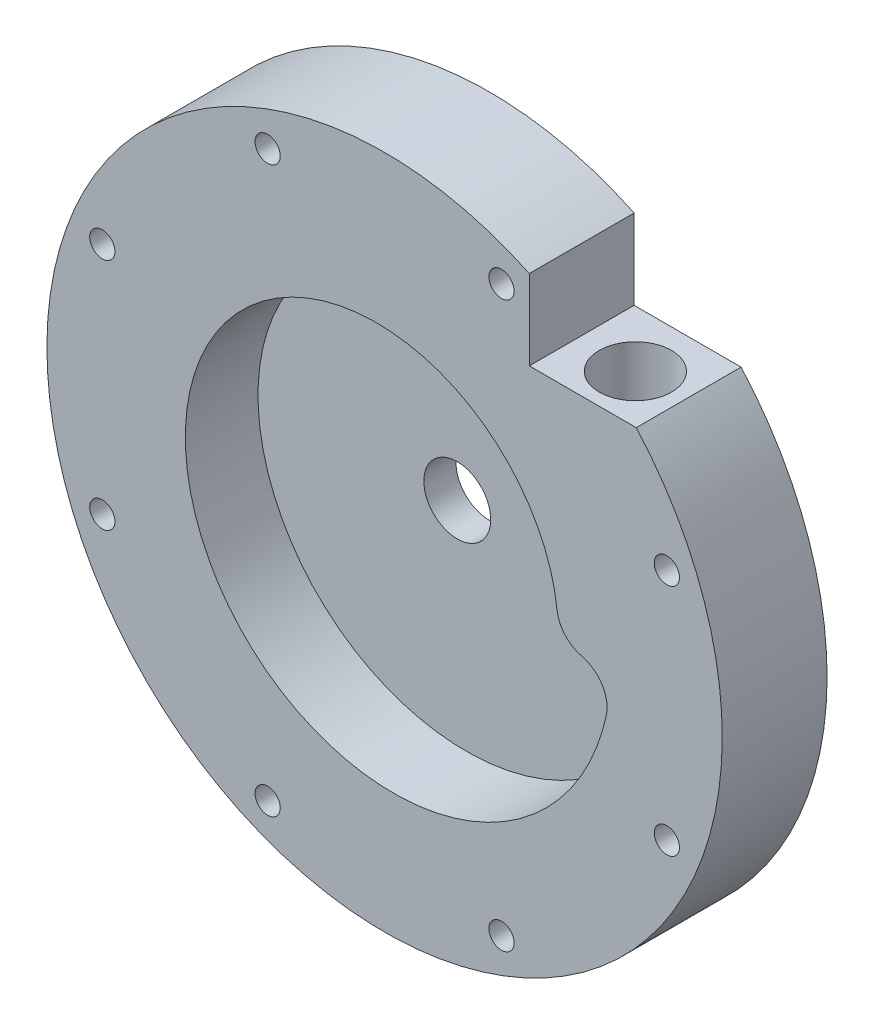
SolidWorks part; units mm, degrees
material "6061-T6 (SS)"
ref_plane "Front Plane" through (0, 0, 0) normal (0, 0, 1) x (1, 0, 0)
ref_plane "Top Plane" through (0, 0, 0) normal (0, 1, 0) x (1, 0, 0)
ref_plane "Right Plane" through (0, 0, 0) normal (1, 0, 0) x (0, 0, -1)
sketch "Sketch22" plane through (0, 0, 0) normal (0, 1, 0) x (1, 0, 0)
  line L0 (-25.4, 0) -> (-6.604, 0)
  line L1 (-25.4, 0) -> (-25.4, -14.351)
  line L2 (-17.4625, 6.35) -> (-17.4625, 4.7625)
  line L3 (-25.4, -14.351) -> (-66.675, -14.351)
  line L4 (-66.675, -14.351) -> (-66.675, 6.35)
  line L9 (-17.4625, 6.35) -> (-66.675, 6.35)
  line L10 (0, 0) -> (0, 9.525) construction
  line L11 (-6.604, 6.35) -> (-6.604, 0)
  line L12 (-17.4625, 4.7625) -> (-11.1125, 4.7625)
  line L15 (-11.1125, 4.7625) -> (-11.1125, 6.35)
  line L16 (-11.1125, 6.35) -> (-6.604, 6.35)
  dimension "D1" = 6.35
  dimension "D2" = 6.35
  dimension "D3" = 20.701
  dimension "D4" = 22.225
  dimension "D5" = 50.8
  dimension "D6" = 133.35
  dimension "D7" = 13.208
  dimension "D8" = 1.5875
revolve "Main Body" add sketch "Sketch22" angle 360 about L10
curve "Volute Spiral"
  spline degree 3 poles (34.2618, 0, 0) (34.2648, 0.0718, 0) (34.2707, 0.2156, 0) (34.2778, 0.4312, 0) (34.2837, 0.647, 0) (34.2882, 0.8628, 0) (34.2914, 1.0787, 0) (34.2932, 1.2947, 0) (34.2937, 1.5108, 0) (34.2929, 1.7269, 0) (34.2907, 1.9431, 0) (34.2871, 2.1593, 0) (34.2822, 2.3756, 0) (34.2759, 2.5919, 0) (34.2683, 2.8082, 0) (34.2593, 3.0245, 0) (34.2489, 3.2407, 0) (34.2372, 3.457, 0) (34.2242, 3.6733, 0) (34.2098, 3.8895, 0) (34.194, 4.1058, 0) (34.1768, 4.3219, 0) (34.1583, 4.538, 0) (34.1385, 4.7541, 0) (34.1173, 4.9701, 0) (34.0947, 5.186, 0) (34.0708, 5.4018, 0) (34.0454, 5.6175, 0) (34.0188, 5.8331, 0) (33.9908, 6.0486, 0) (33.9614, 6.264, 0) (33.9306, 6.4793, 0) (33.8985, 6.6944, 0) (33.8651, 6.9094, 0) (33.8303, 7.1242, 0) (33.7941, 7.3388, 0) (33.7566, 7.5533, 0) (33.7177, 7.7676, 0) (33.6774, 7.9817, 0) (33.6358, 8.1956, 0) (33.5929, 8.4093, 0) (33.5486, 8.6228, 0) (33.5029, 8.8361, 0) (33.4559, 9.0491, 0) (33.4076, 9.2619, 0) (33.3579, 9.4745, 0) (33.3068, 9.6868, 0) (33.2544, 9.8988, 0) (33.2006, 10.1105, 0) (33.1456, 10.322, 0) (33.0891, 10.5332, 0) (33.0313, 10.744, 0) (32.9722, 10.9546, 0) (32.9118, 11.1648, 0) (32.85, 11.3748, 0) (32.7869, 11.5843, 0) (32.7224, 11.7936, 0) (32.6566, 12.0025, 0) (32.5895, 12.211, 0) (32.521, 12.4192, 0) (32.4513, 12.627, 0) (32.3802, 12.8344, 0) (32.3077, 13.0414, 0) (32.234, 13.248, 0) (32.1589, 13.4542, 0) (32.0826, 13.6599, 0) (32.0049, 13.8653, 0) (31.9259, 14.0702, 0) (31.8456, 14.2747, 0) (31.764, 14.4787, 0) (31.6811, 14.6823, 0) (31.5968, 14.8854, 0) (31.5113, 15.088, 0) (31.4245, 15.2901, 0) (31.3364, 15.4917, 0) (31.247, 15.6929, 0) (31.1563, 15.8935, 0) (31.0644, 16.0936, 0) (30.9711, 16.2932, 0) (30.8766, 16.4922, 0) (30.7808, 16.6907, 0) (30.6837, 16.8886, 0) (30.5854, 17.086, 0) (30.4858, 17.2829, 0) (30.3849, 17.4791, 0) (30.2828, 17.6748, 0) (30.1794, 17.8698, 0) (30.0747, 18.0643, 0) (29.9688, 18.2582, 0) (29.8617, 18.4514, 0) (29.7533, 18.644, 0) (29.6437, 18.836, 0) (29.5328, 19.0274, 0) (29.4208, 19.2181, 0) (29.3074, 19.4081, 0) (29.1929, 19.5975, 0) (29.0771, 19.7862, 0) (28.9601, 19.9742, 0) (28.842, 20.1616, 0) (28.7226, 20.3482, 0) (28.602, 20.5342, 0) (28.4801, 20.7194, 0) (28.3571, 20.904, 0) (28.233, 21.0877, 0) (28.1076, 21.2708, 0) (27.981, 21.4531, 0) (27.8533, 21.6347, 0) (27.7243, 21.8155, 0) (27.5942, 21.9956, 0) (27.463, 22.1748, 0) (27.3306, 22.3533, 0) (27.197, 22.531, 0) (27.0623, 22.708, 0) (26.9264, 22.8841, 0) (26.7894, 23.0594, 0) (26.6512, 23.2339, 0) (26.5119, 23.4075, 0) (26.3715, 23.5804, 0) (26.23, 23.7524, 0) (26.0873, 23.9235, 0) (25.9435, 24.0938, 0) (25.7987, 24.2632, 0) (25.6527, 24.4318, 0) (25.5056, 24.5995, 0) (25.3574, 24.7663, 0) (25.2082, 24.9322, 0) (25.0578, 25.0973, 0) (24.9064, 25.2614, 0) (24.7539, 25.4246, 0) (24.6003, 25.5869, 0) (24.4457, 25.7483, 0) (24.29, 25.9087, 0) (24.1333, 26.0682, 0) (23.9755, 26.2268, 0) (23.8167, 26.3844, 0) (23.6569, 26.541, 0) (23.496, 26.6967, 0) (23.3341, 26.8514, 0) (23.1712, 27.0051, 0) (23.0073, 27.1579, 0) (22.8424, 27.3096, 0) (22.6765, 27.4604, 0) (22.5096, 27.6101, 0) (22.3417, 27.7589, 0) (22.1728, 27.9066, 0) (22.003, 28.0533, 0) (21.8322, 28.199, 0) (21.6604, 28.3436, 0) (21.4877, 28.4872, 0) (21.314, 28.6297, 0) (21.1394, 28.7712, 0) (20.9639, 28.9116, 0) (20.7874, 29.051, 0) (20.61, 29.1892, 0) (20.4317, 29.3264, 0) (20.2524, 29.4626, 0) (20.0723, 29.5976, 0) (19.8913, 29.7315, 0) (19.7094, 29.8643, 0) (19.5266, 29.996, 0) (19.3429, 30.1266, 0) (19.1584, 30.2561, 0) (18.973, 30.3844, 0) (18.7867, 30.5116, 0) (18.5996, 30.6377, 0) (18.4117, 30.7626, 0) (18.2229, 30.8864, 0) (18.0333, 31.009, 0) (17.8429, 31.1304, 0) (17.6516, 31.2507, 0) (17.4596, 31.3698, 0) (17.2667, 31.4878, 0) (17.0731, 31.6045, 0) (16.8786, 31.7201, 0) (16.6834, 31.8344, 0) (16.4875, 31.9476, 0) (16.2907, 32.0596, 0) (16.0932, 32.1703, 0) (15.895, 32.2799, 0) (15.696, 32.3882, 0) (15.4963, 32.4953, 0) (15.2959, 32.6012, 0) (15.0947, 32.7058, 0) (14.8929, 32.8092, 0) (14.6903, 32.9114, 0) (14.487, 33.0123, 0) (14.2831, 33.1119, 0) (14.0784, 33.2103, 0) (13.8731, 33.3075, 0) (13.6672, 33.4033, 0) (13.4606, 33.4979, 0) (13.2533, 33.5912, 0) (13.0454, 33.6833, 0) (12.8368, 33.774, 0) (12.6277, 33.8635, 0) (12.4179, 33.9517, 0) (12.2075, 34.0385, 0) (11.9965, 34.1241, 0) (11.7849, 34.2084, 0) (11.5727, 34.2913, 0) (11.36, 34.373, 0) (11.1467, 34.4533, 0) (10.9328, 34.5323, 0) (10.7183, 34.61, 0) (10.5034, 34.6863, 0) (10.2879, 34.7613, 0) (10.0718, 34.835, 0) (9.8553, 34.9074, 0) (9.6382, 34.9783, 0) (9.4206, 35.048, 0) (9.2025, 35.1163, 0) (8.984, 35.1832, 0) (8.765, 35.2488, 0) (8.5455, 35.313, 0) (8.3255, 35.3759, 0) (8.1051, 35.4374, 0) (7.8842, 35.4975, 0) (7.6629, 35.5562, 0) (7.4412, 35.6136, 0) (7.2191, 35.6696, 0) (6.9965, 35.7242, 0) (6.7736, 35.7774, 0) (6.5503, 35.8292, 0) (6.3265, 35.8796, 0) (6.1024, 35.9287, 0) (5.878, 35.9763, 0) (5.6532, 36.0225, 0) (5.428, 36.0674, 0) (5.2025, 36.1108, 0) (4.9766, 36.1528, 0) (4.7505, 36.1934, 0) (4.524, 36.2326, 0) (4.2972, 36.2704, 0) (4.0701, 36.3067, 0) (3.8428, 36.3417, 0) (3.6151, 36.3752, 0) (3.3872, 36.4073, 0) (3.159, 36.438, 0) (2.9306, 36.4672, 0) (2.7019, 36.495, 0) (2.473, 36.5214, 0) (2.2439, 36.5463, 0) (2.0146, 36.5699, 0) (1.785, 36.5919, 0) (1.5553, 36.6126, 0) (1.3253, 36.6318, 0) (1.0952, 36.6495, 0) (0.8649, 36.6658, 0) (0.6345, 36.6807, 0) (0.4039, 36.6941, 0) (0.1731, 36.706, 0) (-0.0577, 36.7166, 0) (-0.2887, 36.7256, 0) (-0.5199, 36.7332, 0) (-0.7511, 36.7394, 0) (-0.9824, 36.7441, 0) (-1.2138, 36.7474, 0) (-1.4453, 36.7492, 0) (-1.6769, 36.7495, 0) (-1.9085, 36.7484, 0) (-2.1402, 36.7458, 0) (-2.3719, 36.7418, 0) (-2.6037, 36.7363, 0) (-2.8355, 36.7293, 0) (-3.0673, 36.7209, 0) (-3.2991, 36.711, 0) (-3.5309, 36.6997, 0) (-3.7627, 36.6869, 0) (-3.9944, 36.6726, 0) (-4.2262, 36.6569, 0) (-4.4579, 36.6397, 0) (-4.6895, 36.6211, 0) (-4.9211, 36.6009, 0) (-5.1526, 36.5794, 0) (-5.3841, 36.5563, 0) (-5.6154, 36.5318, 0) (-5.8467, 36.5059, 0) (-6.0779, 36.4784, 0) (-6.3089, 36.4495, 0) (-6.5399, 36.4192, 0) (-6.7706, 36.3874, 0) (-7.0013, 36.3541, 0) (-7.2318, 36.3194, 0) (-7.4621, 36.2832, 0) (-7.6923, 36.2455, 0) (-7.9223, 36.2064, 0) (-8.1521, 36.1658, 0) (-8.3817, 36.1238, 0) (-8.6111, 36.0803, 0) (-8.8403, 36.0354, 0) (-9.0693, 35.989, 0) (-9.298, 35.9411, 0) (-9.5265, 35.8918, 0) (-9.7548, 35.8411, 0) (-9.9827, 35.7889, 0) (-10.2105, 35.7352, 0) (-10.4379, 35.6802, 0) (-10.665, 35.6236, 0) (-10.8919, 35.5656, 0) (-11.1184, 35.5062, 0) (-11.3446, 35.4453, 0) (-11.5705, 35.383, 0) (-11.7961, 35.3193, 0) (-12.0213, 35.2541, 0) (-12.2461, 35.1875, 0) (-12.4706, 35.1194, 0) (-12.6948, 35.0499, 0) (-12.9185, 34.979, 0) (-13.1419, 34.9067, 0) (-13.3648, 34.8329, 0) (-13.5874, 34.7578, 0) (-13.8095, 34.6812, 0) (-14.0312, 34.6031, 0) (-14.2525, 34.5237, 0) (-14.4734, 34.4429, 0) (-14.6937, 34.3606, 0) (-14.9137, 34.2769, 0) (-15.1331, 34.1918, 0) (-15.3521, 34.1054, 0) (-15.5706, 34.0175, 0) (-15.7885, 33.9282, 0) (-16.006, 33.8375, 0) (-16.223, 33.7455, 0) (-16.4394, 33.652, 0) (-16.6553, 33.5572, 0) (-16.8707, 33.461, 0) (-17.0855, 33.3634, 0) (-17.2997, 33.2644, 0) (-17.5134, 33.164, 0) (-17.7265, 33.0623, 0) (-17.939, 32.9592, 0) (-18.151, 32.8548, 0) (-18.3623, 32.7489, 0) (-18.573, 32.6418, 0) (-18.7831, 32.5332, 0) (-18.9925, 32.4234, 0) (-19.2014, 32.3121, 0) (-19.4095, 32.1996, 0) (-19.6171, 32.0857, 0) (-19.8239, 31.9704, 0) (-20.0301, 31.8538, 0) (-20.2356, 31.7359, 0) (-20.4404, 31.6167, 0) (-20.6445, 31.4962, 0) (-20.8479, 31.3743, 0) (-21.0506, 31.2511, 0) (-21.2526, 31.1267, 0) (-21.4538, 31.0009, 0) (-21.6543, 30.8738, 0) (-21.854, 30.7454, 0) (-22.053, 30.6158, 0) (-22.2512, 30.4848, 0) (-22.4487, 30.3526, 0) (-22.6453, 30.2191, 0) (-22.8412, 30.0843, 0) (-23.0363, 29.9482, 0) (-23.2305, 29.8109, 0) (-23.424, 29.6723, 0) (-23.6166, 29.5325, 0) (-23.8084, 29.3915, 0) (-23.9994, 29.2491, 0) (-24.1895, 29.1056, 0) (-24.3787, 28.9608, 0) (-24.5671, 28.8148, 0) (-24.7546, 28.6676, 0) (-24.9413, 28.5191, 0) (-25.127, 28.3694, 0) (-25.3119, 28.2186, 0) (-25.4958, 28.0665, 0) (-25.6789, 27.9132, 0) (-25.861, 27.7587, 0) (-26.0422, 27.6031, 0) (-26.2224, 27.4463, 0) (-26.4018, 27.2882, 0) (-26.5801, 27.1291, 0) (-26.7576, 26.9687, 0) (-26.934, 26.8072, 0) (-27.1095, 26.6446, 0) (-27.284, 26.4808, 0) (-27.4575, 26.3159, 0) (-27.63, 26.1498, 0) (-27.8015, 25.9826, 0) (-27.972, 25.8143, 0) (-28.1415, 25.6448, 0) (-28.31, 25.4743, 0) (-28.4774, 25.3027, 0) (-28.6438, 25.1299, 0) (-28.8092, 24.9561, 0) (-28.9735, 24.7811, 0) (-29.1367, 24.6051, 0) (-29.2989, 24.4281, 0) (-29.46, 24.2499, 0) (-29.62, 24.0707, 0) (-29.7789, 23.8905, 0) (-29.9368, 23.7092, 0) (-30.0935, 23.5268, 0) (-30.2491, 23.3435, 0) (-30.4036, 23.1591, 0) (-30.557, 22.9737, 0) (-30.7093, 22.7872, 0) (-30.8604, 22.5998, 0) (-31.0104, 22.4114, 0) (-31.1592, 22.2219, 0) (-31.3069, 22.0315, 0) (-31.4534, 21.8402, 0) (-31.5988, 21.6478, 0) (-31.7429, 21.4545, 0) (-31.8859, 21.2602, 0) (-32.0277, 21.065, 0) (-32.1684, 20.8688, 0) (-32.3078, 20.6717, 0) (-32.446, 20.4737, 0) (-32.583, 20.2747, 0) (-32.7188, 20.0748, 0) (-32.8533, 19.8741, 0) (-32.9866, 19.6724, 0) (-33.1187, 19.4698, 0) (-33.2496, 19.2664, 0) (-33.3792, 19.0621, 0) (-33.5075, 18.8569, 0) (-33.6346, 18.6509, 0) (-33.7604, 18.444, 0) (-33.885, 18.2362, 0) (-34.0082, 18.0276, 0) (-34.1302, 17.8182, 0) (-34.2509, 17.608, 0) (-34.3703, 17.397, 0) (-34.4884, 17.1851, 0) (-34.6052, 16.9725, 0) (-34.7207, 16.7591, 0) (-34.8349, 16.5449, 0) (-34.9478, 16.3299, 0) (-35.0593, 16.1141, 0) (-35.1695, 15.8976, 0) (-35.2784, 15.6804, 0) (-35.3859, 15.4624, 0) (-35.4921, 15.2436, 0) (-35.597, 15.0242, 0) (-35.7004, 14.804, 0) (-35.8026, 14.5832, 0) (-35.9033, 14.3616, 0) (-36.0027, 14.1393, 0) (-36.1007, 13.9164, 0) (-36.1973, 13.6928, 0) (-36.2926, 13.4685, 0) (-36.3864, 13.2436, 0) (-36.4789, 13.018, 0) (-36.57, 12.7918, 0) (-36.6596, 12.5649, 0) (-36.7479, 12.3374, 0) (-36.8348, 12.1094, 0) (-36.9202, 11.8807, 0) (-37.0042, 11.6514, 0) (-37.0868, 11.4215, 0) (-37.168, 11.1911, 0) (-37.2477, 10.96, 0) (-37.326, 10.7285, 0) (-37.4029, 10.4963, 0) (-37.4783, 10.2637, 0) (-37.5523, 10.0305, 0) (-37.6248, 9.7967, 0) (-37.6959, 9.5625, 0) (-37.7655, 9.3277, 0) (-37.8337, 9.0925, 0) (-37.9004, 8.8568, 0) (-37.9656, 8.6205, 0) (-38.0293, 8.3839, 0) (-38.0916, 8.1467, 0) (-38.1524, 7.9091, 0) (-38.2117, 7.6711, 0) (-38.2696, 7.4326, 0) (-38.3259, 7.1937, 0) (-38.3808, 6.9544, 0) (-38.4342, 6.7147, 0) (-38.486, 6.4746, 0) (-38.5364, 6.2341, 0) (-38.5853, 5.9932, 0) (-38.6326, 5.7519, 0) (-38.6785, 5.5103, 0) (-38.7229, 5.2684, 0) (-38.7657, 5.0261, 0) (-38.807, 4.7835, 0) (-38.8468, 4.5405, 0) (-38.8851, 4.2973, 0) (-38.9219, 4.0537, 0) (-38.9571, 3.8099, 0) (-38.9908, 3.5657, 0) (-39.023, 3.3213, 0) (-39.0537, 3.0767, 0) (-39.0828, 2.8317, 0) (-39.1104, 2.5866, 0) (-39.1364, 2.3412, 0) (-39.1609, 2.0955, 0) (-39.1839, 1.8497, 0) (-39.2053, 1.6037, 0) (-39.2252, 1.3574, 0) (-39.2435, 1.111, 0) (-39.2603, 0.8644, 0) (-39.2756, 0.6176, 0) (-39.2893, 0.3707, 0) (-39.3014, 0.1236, 0) (-39.312, -0.1236, 0) (-39.321, -0.371, 0) (-39.3285, -0.6185, 0) (-39.3344, -0.866, 0) (-39.3388, -1.1137, 0) (-39.3416, -1.3615, 0) (-39.3428, -1.6093, 0) (-39.3425, -1.8572, 0) (-39.3406, -2.1052, 0) (-39.3372, -2.3532, 0) (-39.3322, -2.6013, 0) (-39.3257, -2.8494, 0) (-39.3175, -3.0975, 0) (-39.3078, -3.3456, 0) (-39.2966, -3.5937, 0) (-39.2838, -3.8418, 0) (-39.2694, -4.0899, 0) (-39.2534, -4.338, 0) (-39.2359, -4.586, 0) (-39.2168, -4.834, 0) (-39.1962, -5.0819, 0) (-39.174, -5.3298, 0) (-39.1502, -5.5776, 0) (-39.1248, -5.8252, 0) (-39.0979, -6.0728, 0) (-39.0694, -6.3203, 0) (-39.0394, -6.5677, 0) (-39.0078, -6.8149, 0) (-38.9746, -7.062, 0) (-38.9399, -7.309, 0) (-38.9036, -7.5558, 0) (-38.8657, -7.8024, 0) (-38.8263, -8.0488, 0) (-38.7853, -8.2951, 0) (-38.7427, -8.5411, 0) (-38.6986, -8.787, 0) (-38.653, -9.0326, 0) (-38.6057, -9.2781, 0) (-38.557, -9.5232, 0) (-38.5066, -9.7682, 0) (-38.4547, -10.0128, 0) (-38.4013, -10.2572, 0) (-38.3463, -10.5014, 0) (-38.2897, -10.7452, 0) (-38.2316, -10.9888, 0) (-38.172, -11.232, 0) (-38.1108, -11.475, 0) (-38.048, -11.7176, 0) (-37.9838, -11.9598, 0) (-37.9179, -12.2018, 0) (-37.8506, -12.4433, 0) (-37.7817, -12.6845, 0) (-37.7112, -12.9254, 0) (-37.6393, -13.1658, 0) (-37.5658, -13.4059, 0) (-37.4907, -13.6455, 0) (-37.4142, -13.8848, 0) (-37.3361, -14.1236, 0) (-37.2565, -14.362, 0) (-37.1753, -14.5999, 0) (-37.0927, -14.8374, 0) (-37.0085, -15.0744, 0) (-36.9228, -15.311, 0) (-36.8357, -15.547, 0) (-36.747, -15.7826, 0) (-36.6568, -16.0177, 0) (-36.5651, -16.2523, 0) (-36.4719, -16.4863, 0) (-36.3772, -16.7199, 0) (-36.281, -16.9528, 0) (-36.1833, -17.1853, 0) (-36.0841, -17.4172, 0) (-35.9834, -17.6485, 0) (-35.8813, -17.8792, 0) (-35.7777, -18.1094, 0) (-35.6726, -18.3389, 0) (-35.566, -18.5679, 0) (-35.458, -18.7962, 0) (-35.3485, -19.0239, 0) (-35.2376, -19.251, 0) (-35.1251, -19.4774, 0) (-35.0113, -19.7032, 0) (-34.896, -19.9283, 0) (-34.7792, -20.1528, 0) (-34.661, -20.3765, 0) (-34.5414, -20.5996, 0) (-34.4203, -20.822, 0) (-34.2978, -21.0437, 0) (-34.1738, -21.2646, 0) (-34.0485, -21.4849, 0) (-33.9217, -21.7044, 0) (-33.7935, -21.9231, 0) (-33.6639, -22.1411, 0) (-33.5329, -22.3584, 0) (-33.4005, -22.5748, 0) (-33.2667, -22.7905, 0) (-33.1315, -23.0054, 0) (-32.995, -23.2195, 0) (-32.857, -23.4328, 0) (-32.7177, -23.6453, 0) (-32.577, -23.8569, 0) (-32.4349, -24.0677, 0) (-32.2915, -24.2777, 0) (-32.1467, -24.4868, 0) (-32.0006, -24.6951, 0) (-31.8531, -24.9025, 0) (-31.7042, -25.109, 0) (-31.5541, -25.3146, 0) (-31.4026, -25.5194, 0) (-31.2497, -25.7232, 0) (-31.0956, -25.9261, 0) (-30.9401, -26.1281, 0) (-30.7833, -26.3292, 0) (-30.6253, -26.5293, 0) (-30.4659, -26.7285, 0) (-30.3052, -26.9267, 0) (-30.1433, -27.124, 0) (-29.98, -27.3203, 0) (-29.8155, -27.5156, 0) (-29.6497, -27.7099, 0) (-29.4827, -27.9032, 0) (-29.3144, -28.0956, 0) (-29.1448, -28.2869, 0) (-28.974, -28.4772, 0) (-28.8019, -28.6664, 0) (-28.6287, -28.8546, 0) (-28.4542, -29.0418, 0) (-28.2784, -29.2279, 0) (-28.1015, -29.413, 0) (-27.9233, -29.597, 0) (-27.744, -29.7799, 0) (-27.5634, -29.9618, 0) (-27.3817, -30.1425, 0) (-27.1987, -30.3221, 0) (-27.0146, -30.5007, 0) (-26.8294, -30.6781, 0) (-26.6429, -30.8544, 0) (-26.4554, -31.0296, 0) (-26.2666, -31.2036, 0) (-26.0767, -31.3765, 0) (-25.8857, -31.5482, 0) (-25.6936, -31.7188, 0) (-25.5003, -31.8882, 0) (-25.306, -32.0564, 0) (-25.1105, -32.2234, 0) (-24.9139, -32.3893, 0) (-24.7162, -32.5539, 0) (-24.5175, -32.7174, 0) (-24.3176, -32.8796, 0) (-24.1167, -33.0406, 0) (-23.9147, -33.2004, 0) (-23.7117, -33.359, 0) (-23.5076, -33.5163, 0) (-23.3025, -33.6724, 0) (-23.0964, -33.8272, 0) (-22.8892, -33.9807, 0) (-22.681, -34.133, 0) (-22.4718, -34.2841, 0) (-22.2616, -34.4338, 0) (-22.0504, -34.5822, 0) (-21.8382, -34.7294, 0) (-21.6251, -34.8752, 0) (-21.4109, -35.0198, 0) (-21.1959, -35.163, 0) (-20.9798, -35.3049, 0) (-20.7628, -35.4455, 0) (-20.5449, -35.5848, 0) (-20.326, -35.7227, 0) (-20.1062, -35.8593, 0) (-19.8855, -35.9945, 0) (-19.6639, -36.1284, 0) (-19.4414, -36.2609, 0) (-19.2181, -36.392, 0) (-18.9938, -36.5218, 0) (-18.7686, -36.6502, 0) (-18.5426, -36.7772, 0) (-18.3158, -36.9028, 0) (-18.0881, -37.027, 0) (-17.8595, -37.1498, 0) (-17.6302, -37.2712, 0) (-17.4, -37.3911, 0) (-17.169, -37.5097, 0) (-16.9372, -37.6268, 0) (-16.7046, -37.7425, 0) (-16.4712, -37.8568, 0) (-16.237, -37.9696, 0) (-16.0021, -38.081, 0) (-15.7664, -38.1909, 0) (-15.53, -38.2994, 0) (-15.2928, -38.4064, 0) (-15.0549, -38.5119, 0) (-14.8163, -38.616, 0) (-14.577, -38.7185, 0) (-14.3369, -38.8196, 0) (-14.0962, -38.9192, 0) (-13.8547, -39.0174, 0) (-13.6126, -39.114, 0) (-13.3699, -39.2091, 0) (-13.1265, -39.3027, 0) (-12.8824, -39.3949, 0) (-12.6377, -39.4854, 0) (-12.3923, -39.5745, 0) (-12.1464, -39.6621, 0) (-11.8998, -39.7481, 0) (-11.6526, -39.8326, 0) (-11.4048, -39.9155, 0) (-11.1565, -39.997, 0) (-10.9076, -40.0768, 0) (-10.6581, -40.1552, 0) (-10.408, -40.2319, 0) (-10.1575, -40.3071, 0) (-9.9063, -40.3808, 0) (-9.6547, -40.4529, 0) (-9.4025, -40.5234, 0) (-9.1499, -40.5924, 0) (-8.8967, -40.6598, 0) (-8.6431, -40.7256, 0) (-8.389, -40.7898, 0) (-8.1344, -40.8524, 0) (-7.8793, -40.9135, 0) (-7.6239, -40.9729, 0) (-7.3679, -41.0308, 0) (-7.1116, -41.087, 0) (-6.8548, -41.1417, 0) (-6.5977, -41.1948, 0) (-6.3401, -41.2462, 0) (-6.0821, -41.2961, 0) (-5.8238, -41.3443, 0) (-5.5651, -41.3909, 0) (-5.3061, -41.4359, 0) (-5.0467, -41.4793, 0) (-4.7869, -41.5211, 0) (-4.5269, -41.5612, 0) (-4.2665, -41.5997, 0) (-4.0058, -41.6366, 0) (-3.7449, -41.6718, 0) (-3.4836, -41.7054, 0) (-3.2221, -41.7374, 0) (-2.9603, -41.7677, 0) (-2.6982, -41.7964, 0) (-2.4359, -41.8234, 0) (-2.1734, -41.8488, 0) (-1.9106, -41.8726, 0) (-1.6477, -41.8947, 0) (-1.3845, -41.9151, 0) (-1.1212, -41.9339, 0) (-0.8576, -41.9511, 0) (-0.5939, -41.9666, 0) (-0.33, -41.9804, 0) (-0.066, -41.9926, 0) (0.1981, -42.0031, 0) (0.4624, -42.012, 0) (0.7268, -42.0192, 0) (0.9914, -42.0247, 0) (1.256, -42.0286, 0) (1.5207, -42.0308, 0) (1.7855, -42.0313, 0) (2.0503, -42.0302, 0) (2.3152, -42.0274, 0) (2.5802, -42.0229, 0) (2.8452, -42.0168, 0) (3.1102, -42.0089, 0) (3.3752, -41.9995, 0) (3.6403, -41.9883, 0) (3.9053, -41.9755, 0) (4.1703, -41.961, 0) (4.4353, -41.9448, 0) (4.7002, -41.927, 0) (4.9651, -41.9075, 0) (5.2299, -41.8863, 0) (5.4947, -41.8634, 0) (5.7594, -41.8389, 0) (6.024, -41.8127, 0) (6.2885, -41.7848, 0) (6.5528, -41.7553, 0) (6.8171, -41.7241, 0) (7.0812, -41.6912, 0) (7.3452, -41.6566, 0) (7.609, -41.6204, 0) (7.8727, -41.5825, 0) (8.1362, -41.5429, 0) (8.3995, -41.5017, 0) (8.6626, -41.4588, 0) (8.9254, -41.4142, 0) (9.1881, -41.3679, 0) (9.4506, -41.32, 0) (9.7128, -41.2705, 0) (9.9747, -41.2192, 0) (10.2364, -41.1663, 0) (10.4979, -41.1118, 0) (10.759, -41.0556, 0) (11.0199, -40.9977, 0) (11.2804, -40.9382, 0) (11.5407, -40.877, 0) (11.8006, -40.8141, 0) (12.0602, -40.7496, 0) (12.3194, -40.6835, 0) (12.5783, -40.6157, 0) (12.8368, -40.5463, 0) (13.0949, -40.4752, 0) (13.3527, -40.4025, 0) (13.6101, -40.3281, 0) (13.867, -40.2521, 0) (14.1235, -40.1745, 0) (14.3797, -40.0952, 0) (14.6353, -40.0143, 0) (14.8905, -39.9318, 0) (15.1453, -39.8476, 0) (15.3996, -39.7618, 0) (15.6534, -39.6744, 0) (15.9067, -39.5854, 0) (16.1596, -39.4948, 0) (16.4119, -39.4025, 0) (16.6637, -39.3087, 0) (16.9149, -39.2132, 0) (17.1657, -39.1161, 0) (17.4158, -39.0174, 0) (17.6654, -38.9172, 0) (17.9145, -38.8153, 0) (18.1629, -38.7118, 0) (18.4108, -38.6068, 0) (18.658, -38.5001, 0) (18.9047, -38.3919, 0) (19.1507, -38.2821, 0) (19.3961, -38.1707, 0) (19.6408, -38.0578, 0) (19.8849, -37.9433, 0) (20.1283, -37.8272, 0) (20.3711, -37.7095, 0) (20.6132, -37.5904, 0) (20.8546, -37.4696, 0) (21.0952, -37.3473, 0) (21.3352, -37.2235, 0) (21.5744, -37.0981, 0) (21.8129, -36.9712, 0) (22.0507, -36.8427, 0) (22.2877, -36.7127, 0) (22.524, -36.5812, 0) (22.7594, -36.4482, 0) (22.9941, -36.3137, 0) (23.228, -36.1776, 0) (23.4611, -36.0401, 0) (23.6934, -35.901, 0) (23.9249, -35.7605, 0) (24.1556, -35.6184, 0) (24.3854, -35.4749, 0) (24.6143, -35.3299, 0) (24.8424, -35.1834, 0) (25.0696, -35.0355, 0) (25.296, -34.8861, 0) (25.5214, -34.7352, 0) (25.746, -34.5828, 0) (25.9696, -34.4291, 0) (26.1924, -34.2738, 0) (26.4142, -34.1172, 0) (26.6351, -33.9591, 0) (26.855, -33.7995, 0) (27.074, -33.6386, 0) (27.292, -33.4762, 0) (27.5091, -33.3124, 0) (27.7252, -33.1472, 0) (27.9402, -32.9807, 0) (28.1543, -32.8127, 0) (28.3674, -32.6433, 0) (28.5795, -32.4726, 0) (28.7905, -32.3004, 0) (29.0005, -32.127, 0) (29.2095, -31.9521, 0) (29.4174, -31.7759, 0) (29.6242, -31.5983, 0) (29.83, -31.4194, 0) (30.0347, -31.2392, 0) (30.2383, -31.0576, 0) (30.4408, -30.8747, 0) (30.6422, -30.6905, 0) (30.8426, -30.5049, 0) (31.0417, -30.3181, 0) (31.2398, -30.1299, 0) (31.4367, -29.9405, 0) (31.6325, -29.7498, 0) (31.8271, -29.5578, 0) (32.0205, -29.3645, 0) (32.2128, -29.17, 0) (32.4039, -28.9742, 0) (32.5938, -28.7772, 0) (32.7825, -28.5789, 0) (32.97, -28.3794, 0) (33.1563, -28.1787, 0) (33.3414, -27.9767, 0) (33.5252, -27.7736, 0) (33.7079, -27.5692, 0) (33.8892, -27.3636, 0) (34.0693, -27.1569, 0) (34.2482, -26.9489, 0) (34.4258, -26.7398, 0) (34.6021, -26.5295, 0) (34.7771, -26.3181, 0) (34.9509, -26.1055, 0) (35.1233, -25.8917, 0) (35.2944, -25.6768, 0) (35.4643, -25.4608, 0) (35.6328, -25.2437, 0) (35.7999, -25.0255, 0) (35.9658, -24.8061, 0) (36.1303, -24.5857, 0) (36.2934, -24.3641, 0) (36.4552, -24.1415, 0) (36.6157, -23.9179, 0) (36.7747, -23.6931, 0) (36.9324, -23.4673, 0) (37.0887, -23.2405, 0) (37.2436, -23.0126, 0) (37.3971, -22.7837, 0) (37.5492, -22.5538, 0) (37.6999, -22.3228, 0) (37.8491, -22.0909, 0) (37.997, -21.858, 0) (38.1434, -21.624, 0) (38.2884, -21.3891, 0) (38.4319, -21.1533, 0) (38.574, -20.9165, 0) (38.7146, -20.6787, 0) (38.8537, -20.44, 0) (38.9914, -20.2003, 0) (39.1276, -19.9598, 0) (39.2623, -19.7183, 0) (39.3956, -19.4759, 0) (39.5273, -19.2326, 0) (39.6575, -18.9884, 0) (39.7863, -18.7434, 0) (39.9135, -18.4975, 0) (40.0392, -18.2507, 0) (40.1633, -18.0031, 0) (40.286, -17.7546, 0) (40.4071, -17.5053, 0) (40.5267, -17.2552, 0) (40.6447, -17.0043, 0) (40.7611, -16.7525, 0) (40.876, -16.5, 0) (40.9894, -16.2467, 0) (41.1012, -15.9927, 0) (41.2114, -15.7378, 0) (41.32, -15.4822, 0) (41.427, -15.2259, 0) (41.5325, -14.9688, 0) (41.6363, -14.711, 0) (41.7386, -14.4525, 0) (41.8392, -14.1933, 0) (41.9383, -13.9334, 0) (42.0357, -13.6728, 0) (42.1315, -13.4116, 0) (42.2257, -13.1496, 0) (42.3182, -12.8871, 0) (42.4092, -12.6238, 0) (42.4985, -12.36, 0) (42.5861, -12.0955, 0) (42.6721, -11.8304, 0) (42.7565, -11.5647, 0) (42.8392, -11.2984, 0) (42.9202, -11.0315, 0) (42.9996, -10.7641, 0) (43.0773, -10.4961, 0) (43.1534, -10.2275, 0) (43.2277, -9.9584, 0) (43.3004, -9.6888, 0) (43.3715, -9.4186, 0) (43.4408, -9.148, 0) (43.5084, -8.8768, 0) (43.5744, -8.6052, 0) (43.6386, -8.333, 0) (43.7012, -8.0604, 0) (43.7621, -7.7874, 0) (43.8212, -7.5139, 0) (43.8786, -7.24, 0) (43.9344, -6.9656, 0) (43.9884, -6.6908, 0) (44.0407, -6.4156, 0) (44.0913, -6.1401, 0) (44.1401, -5.8641, 0) (44.1872, -5.5878, 0) (44.2326, -5.3111, 0) (44.2763, -5.0341, 0) (44.3182, -4.7567, 0) (44.3584, -4.479, 0) (44.3969, -4.201, 0) (44.4336, -3.9226, 0) (44.4686, -3.644, 0) (44.5018, -3.3651, 0) (44.5333, -3.0859, 0) (44.563, -2.8065, 0) (44.591, -2.5268, 0) (44.6172, -2.2468, 0) (44.6416, -1.9667, 0) (44.6643, -1.6863, 0) (44.6853, -1.4057, 0) (44.7044, -1.1249, 0) (44.7219, -0.8439, 0) (44.7375, -0.5628, 0) (44.7515, -0.2815, 0) (44.7593, -0.0938, 0) (44.7632, 0, 0) knots 0 0 0 0 0.000871 0.001743 0.002614 0.003486 0.004358 0.005231 0.006103 0.006976 0.007849 0.008723 0.009596 0.01047 0.011344 0.012219 0.013093 0.013968 0.014843 0.015718 0.016594 0.017469 0.018345 0.019222 0.020098 0.020975 0.021852 0.022729 0.023606 0.024484 0.025362 0.02624 0.027119 0.027997 0.028876 0.029755 0.030635 0.031514 0.032394 0.033274 0.034154 0.035035 0.035916 0.036797 0.037678 0.03856 0.039442 0.040324 0.041206 0.042089 0.042971 0.043854 0.044738 0.045621 0.046505 0.047389 0.048273 0.049158 0.050042 0.050927 0.051813 0.052698 0.053584 0.05447 0.055356 0.056242 0.057129 0.058016 0.058903 0.059791 0.060678 0.061566 0.062454 0.063343 0.064232 0.06512 0.06601 0.066899 0.067789 0.068679 0.069569 0.070459 0.07135 0.072241 0.073132 0.074023 0.074915 0.075807 0.076699 0.077591 0.078484 0.079377 0.08027 0.081163 0.082057 0.082951 0.083845 0.084739 0.085634 0.086529 0.087424 0.088319 0.089215 0.090111 0.091007 0.091903 0.0928 0.093696 0.094594 0.095491 0.096388 0.097286 0.098184 0.099083 0.099981 0.10088 0.101779 0.102679 0.103578 0.104478 0.105378 0.106279 0.107179 0.10808 0.108981 0.109882 0.110784 0.111686 0.112588 0.11349 0.114393 0.115296 0.116199 0.117102 0.118006 0.11891 0.119814 0.120718 0.121623 0.122528 0.123433 0.124338 0.125244 0.12615 0.127056 0.127962 0.128869 0.129776 0.130683 0.13159 0.132498 0.133406 0.134314 0.135222 0.136131 0.13704 0.137949 0.138858 0.139768 0.140678 0.141588 0.142498 0.143409 0.14432 0.145231 0.146142 0.147054 0.147966 0.148878 0.149791 0.150703 0.151616 0.152529 0.153443 0.154357 0.155271 0.156185 0.157099 0.158014 0.158929 0.159844 0.16076 0.161675 0.162591 0.163508 0.164424 0.165341 0.166258 0.167175 0.168093 0.16901 0.169928 0.170847 0.171765 0.172684 0.173603 0.174522 0.175442 0.176362 0.177282 0.178202 0.179123 0.180044 0.180965 0.181886 0.182808 0.183729 0.184652 0.185574 0.186497 0.187419 0.188343 0.189266 0.19019 0.191113 0.192038 0.192962 0.193887 0.194812 0.195737 0.196662 0.197588 0.198514 0.19944 0.200367 0.201293 0.20222 0.203147 0.204075 0.205003 0.205931 0.206859 0.207787 0.208716 0.209645 0.210575 0.211504 0.212434 0.213364 0.214294 0.215225 0.216156 0.217087 0.218018 0.21895 0.219882 0.220814 0.221746 0.222679 0.223612 0.224545 0.225478 0.226412 0.227346 0.22828 0.229214 0.230149 0.231084 0.232019 0.232955 0.23389 0.234826 0.235763 0.236699 0.237636 0.238573 0.23951 0.240448 0.241386 0.242324 0.243262 0.244201 0.245139 0.246078 0.247018 0.247957 0.248897 0.249837 0.250778 0.251718 0.252659 0.253601 0.254542 0.255484 0.256426 0.257368 0.25831 0.259253 0.260196 0.261139 0.262083 0.263027 0.263971 0.264915 0.265859 0.266804 0.267749 0.268695 0.26964 0.270586 0.271532 0.272479 0.273425 0.274372 0.275319 0.276267 0.277214 0.278162 0.27911 0.280059 0.281008 0.281957 0.282906 0.283855 0.284805 0.285755 0.286705 0.287656 0.288607 0.289558 0.290509 0.291461 0.292413 0.293365 0.294317 0.29527 0.296223 0.297176 0.298129 0.299083 0.300037 0.300991 0.301946 0.3029 0.303855 0.30481 0.305766 0.306722 0.307678 0.308634 0.309591 0.310548 0.311505 0.312462 0.31342 0.314377 0.315336 0.316294 0.317253 0.318212 0.319171 0.32013 0.32109 0.32205 0.32301 0.323971 0.324931 0.325892 0.326854 0.327815 0.328777 0.329739 0.330702 0.331664 0.332627 0.33359 0.334554 0.335517 0.336481 0.337445 0.33841 0.339375 0.34034 0.341305 0.34227 0.343236 0.344202 0.345168 0.346135 0.347102 0.348069 0.349036 0.350004 0.350972 0.35194 0.352908 0.353877 0.354846 0.355815 0.356785 0.357754 0.358724 0.359695 0.360665 0.361636 0.362607 0.363578 0.36455 0.365522 0.366494 0.367466 0.368439 0.369412 0.370385 0.371358 0.372332 0.373306 0.37428 0.375255 0.37623 0.377205 0.37818 0.379156 0.380131 0.381107 0.382084 0.38306 0.384037 0.385015 0.385992 0.38697 0.387948 0.388926 0.389904 0.390883 0.391862 0.392841 0.393821 0.394801 0.395781 0.396761 0.397742 0.398723 0.399704 0.400685 0.401667 0.402649 0.403631 0.404614 0.405596 0.406579 0.407563 0.408546 0.40953 0.410514 0.411498 0.412483 0.413468 0.414453 0.415438 0.416424 0.41741 0.418396 0.419383 0.420369 0.421357 0.422344 0.423331 0.424319 0.425307 0.426296 0.427284 0.428273 0.429262 0.430252 0.431241 0.432231 0.433222 0.434212 0.435203 0.436194 0.437185 0.438177 0.439169 0.440161 0.441153 0.442146 0.443139 0.444132 0.445125 0.446119 0.447113 0.448107 0.449102 0.450096 0.451091 0.452087 0.453082 0.454078 0.455074 0.456071 0.457067 0.458064 0.459061 0.460059 0.461057 0.462055 0.463053 0.464051 0.46505 0.466049 0.467049 0.468048 0.469048 0.470048 0.471049 0.472049 0.47305 0.474052 0.475053 0.476055 0.477057 0.478059 0.479062 0.480065 0.481068 0.482071 0.483075 0.484079 0.485083 0.486087 0.487092 0.488097 0.489102 0.490108 0.491114 0.49212 0.493126 0.494133 0.49514 0.496147 0.497154 0.498162 0.49917 0.500178 0.501187 0.502196 0.503205 0.504214 0.505224 0.506233 0.507244 0.508254 0.509265 0.510276 0.511287 0.512298 0.51331 0.514322 0.515334 0.516347 0.51736 0.518373 0.519386 0.5204 0.521414 0.522428 0.523442 0.524457 0.525472 0.526488 0.527503 0.528519 0.529535 0.530551 0.531568 0.532585 0.533602 0.53462 0.535637 0.536655 0.537673 0.538692 0.539711 0.54073 0.541749 0.542769 0.543789 0.544809 0.545829 0.54685 0.547871 0.548892 0.549914 0.550936 0.551958 0.55298 0.554003 0.555026 0.556049 0.557072 0.558096 0.55912 0.560144 0.561169 0.562193 0.563218 0.564244 0.565269 0.566295 0.567321 0.568348 0.569375 0.570402 0.571429 0.572456 0.573484 0.574512 0.575541 0.576569 0.577598 0.578627 0.579657 0.580686 0.581716 0.582747 0.583777 0.584808 0.585839 0.58687 0.587902 0.588934 0.589966 0.590998 0.592031 0.593064 0.594097 0.595131 0.596165 0.597199 0.598233 0.599268 0.600303 0.601338 0.602373 0.603409 0.604445 0.605481 0.606518 0.607554 0.608592 0.609629 0.610667 0.611704 0.612743 0.613781 0.61482 0.615859 0.616898 0.617938 0.618977 0.620018 0.621058 0.622099 0.62314 0.624181 0.625222 0.626264 0.627306 0.628348 0.629391 0.630434 0.631477 0.63252 0.633564 0.634608 0.635652 0.636697 0.637741 0.638786 0.639832 0.640877 0.641923 0.642969 0.644016 0.645062 0.646109 0.647157 0.648204 0.649252 0.6503 0.651348 0.652397 0.653446 0.654495 0.655545 0.656594 0.657644 0.658695 0.659745 0.660796 0.661847 0.662898 0.66395 0.665002 0.666054 0.667107 0.668159 0.669212 0.670266 0.671319 0.672373 0.673427 0.674482 0.675536 0.676591 0.677647 0.678702 0.679758 0.680814 0.68187 0.682927 0.683984 0.685041 0.686099 0.687156 0.688214 0.689273 0.690331 0.69139 0.692449 0.693508 0.694568 0.695628 0.696688 0.697749 0.69881 0.699871 0.700932 0.701994 0.703055 0.704118 0.70518 0.706243 0.707306 0.708369 0.709433 0.710496 0.71156 0.712625 0.713689 0.714754 0.71582 0.716885 0.717951 0.719017 0.720083 0.72115 0.722217 0.723284 0.724351 0.725419 0.726487 0.727555 0.728624 0.729693 0.730762 0.731831 0.732901 0.733971 0.735041 0.736111 0.737182 0.738253 0.739324 0.740396 0.741468 0.74254 0.743612 0.744685 0.745758 0.746831 0.747905 0.748979 0.750053 0.751127 0.752202 0.753277 0.754352 0.755428 0.756503 0.757579 0.758656 0.759732 0.760809 0.761886 0.762964 0.764041 0.765119 0.766198 0.767276 0.768355 0.769434 0.770514 0.771593 0.772673 0.773754 0.774834 0.775915 0.776996 0.778077 0.779159 0.780241 0.781323 0.782405 0.783488 0.784571 0.785654 0.786738 0.787822 0.788906 0.789991 0.791075 0.79216 0.793245 0.794331 0.795417 0.796503 0.797589 0.798676 0.799763 0.80085 0.801938 0.803025 0.804113 0.805202 0.80629 0.807379 0.808468 0.809558 0.810648 0.811738 0.812828 0.813919 0.815009 0.816101 0.817192 0.818284 0.819376 0.820468 0.82156 0.822653 0.823746 0.82484 0.825933 0.827027 0.828122 0.829216 0.830311 0.831406 0.832501 0.833597 0.834693 0.835789 0.836885 0.837982 0.839079 0.840177 0.841274 0.842372 0.84347 0.844569 0.845667 0.846766 0.847866 0.848965 0.850065 0.851165 0.852266 0.853366 0.854467 0.855568 0.85667 0.857772 0.858874 0.859976 0.861079 0.862182 0.863285 0.864389 0.865492 0.866596 0.867701 0.868805 0.86991 0.871016 0.872121 0.873227 0.874333 0.875439 0.876546 0.877653 0.87876 0.879867 0.880975 0.882083 0.883191 0.8843 0.885409 0.886518 0.887627 0.888737 0.889847 0.890957 0.892068 0.893179 0.89429 0.895401 0.896513 0.897625 0.898737 0.89985 0.900962 0.902075 0.903189 0.904303 0.905416 0.906531 0.907645 0.90876 0.909875 0.91099 0.912106 0.913222 0.914338 0.915455 0.916571 0.917689 0.918806 0.919923 0.921041 0.92216 0.923278 0.924397 0.925516 0.926635 0.927755 0.928875 0.929995 0.931115 0.932236 0.933357 0.934478 0.9356 0.936722 0.937844 0.938966 0.940089 0.941212 0.942335 0.943459 0.944583 0.945707 0.946831 0.947956 0.949081 0.950206 0.951332 0.952458 0.953584 0.95471 0.955837 0.956964 0.958091 0.959219 0.960347 0.961475 0.962603 0.963732 0.964861 0.96599 0.96712 0.968249 0.96938 0.97051 0.971641 0.972772 0.973903 0.975034 0.976166 0.977298 0.978431 0.979563 0.980696 0.981829 0.982963 0.984097 0.985231 0.986365 0.9875 0.988635 0.98977 0.990906 0.992041 0.993178 0.994314 0.995451 0.996587 0.997725 0.998862 1 1 1 1
sketch "Sketch23" plane through (0, 0, 0) normal (0, 0, 1) x (1, 0, 0)
  arc A9 (43.785, -7.6808) -> (38.9283, 0) centre (37.4553, -6.3073) ccw
  arc A10 (38.9283, 0) -> (34.0645, 5.4541) centre (40.3725, 6.1836) cw
  spline S1 degree 3 poles (2030.2811, -117.0653) (22.7633, -27.2168) (33.8126, -13.6289) (34.2778, 0.4312) (34.2837, 0.647) (34.2927, 1.0788) (34.2982, 2.0882) (34.2447, 3.6037) (34.0848, 5.4046) (33.8442, 7.1278) (33.5167, 8.8404) (33.1027, 10.5382) (32.6028, 12.2167) (32.018, 13.8717) (31.3492, 15.4988) (30.5978, 17.0937) (29.7654, 18.6523) (28.8536, 20.1705) (27.8645, 21.6442) (26.8001, 23.0695) (25.6629, 24.4425) (24.4554, 25.7594) (23.1804, 27.0168) (21.8408, 28.2111) (20.4397, 29.3391) (18.9803, 30.3974) (17.4663, 31.3832) (15.901, 32.2936) (14.2884, 33.126) (12.6323, 33.8779) (10.9367, 34.5469) (9.2057, 35.1311) (7.4437, 35.6286) (5.6549, 36.0377) (3.8437, 36.3569) (2.0147, 36.5852) (0.1725, 36.7214) (-1.6783, 36.7648) (-3.533, 36.7149) (-5.387, 36.5715) (-7.2355, 36.3344) (-9.0737, 36.0038) (-10.8971, 35.5803) (-12.7007, 35.0643) (-14.48, 34.457) (-16.2304, 33.7593) (-17.9471, 32.9726) (-19.6258, 32.0987) (-21.262, 31.1393) (-22.8513, 30.0964) (-24.3894, 28.9724) (-25.8723, 27.7699) (-27.2958, 26.4914) (-28.6562, 25.1399) (-29.9497, 23.7185) (-31.1726, 22.2307) (-32.3216, 20.6797) (-33.3934, 19.0694) (-34.385, 17.4036) (-35.2934, 15.6863) (-36.116, 13.9216) (-36.8503, 12.1138) (-37.4941, 10.2673) (-38.0454, 8.3867) (-38.5022, 6.4766) (-38.8631, 4.5417) (-39.1267, 2.587) (-39.292, 0.6172) (-39.358, -1.3627) (-39.3242, -3.3477) (-39.1902, -5.3327) (-38.956, -7.3127) (-38.6217, -9.2826) (-38.1877, -11.2374) (-37.6547, -13.172) (-37.0237, -15.0814) (-36.2958, -16.9606) (-35.4725, -18.8047) (-34.5554, -20.6088) (-33.5465, -22.3683) (-32.448, -24.0784) (-31.2623, -25.7345) (-29.9921, -27.3322) (-28.6401, -28.8672) (-27.2096, -30.3353) (-25.7038, -31.7324) (-24.1262, -33.0548) (-22.4806, -34.2987) (-20.7709, -35.4607) (-19.0011, -36.5374) (-17.1755, -37.5256) (-15.2985, -38.4226) (-13.3748, -39.2257) (-11.4089, -39.9324) (-9.4058, -40.5405) (-7.3703, -41.048) (-5.3076, -41.4533) (-3.2227, -41.7548) (-1.1209, -41.9515) (0.9925, -42.0422) (3.1122, -42.0264) (5.2328, -41.9037) (7.349, -41.6739) (9.4552, -41.3371) (11.5462, -40.8938) (13.6164, -40.3447) (15.6606, -39.6907) (17.6735, -38.9331) (19.6497, -38.0733) (21.5841, -37.1132) (23.4715, -36.0547) (25.3071, -34.9002) (27.0859, -33.6522) (28.8031, -32.3134) (30.4541, -30.887) (32.0344, -29.3763) (33.5397, -27.7846) (34.9659, -26.1158) (36.309, -24.3737) (37.5652, -22.5626) (38.7311, -20.6867) (39.8032, -18.7505) (40.7784, -16.7589) (41.6539, -14.7165) (42.4271, -12.6284) (43.0955, -10.4997) (43.657, -8.3358) (44.1098, -6.1419) (44.4379, -4.0162) (44.6062, -2.4335) (44.6789, -1.4992) (44.7044, -1.1249) (44.7219, -0.8439) (44.7375, -0.5628) (45.566, 16.1056) (34.6961, 33.2048) (2043.9061, -40.4097) knots -0.16783 -0.16783 -0.16783 -0.16783 0.000871 0.001743 0.002614 0.003486 0.006976 0.014843 0.021852 0.028876 0.035916 0.042971 0.050042 0.057129 0.064232 0.07135 0.078484 0.085634 0.0928 0.099981 0.107179 0.114393 0.121623 0.128869 0.136131 0.143409 0.150703 0.158014 0.165341 0.172684 0.180044 0.187419 0.194812 0.20222 0.209645 0.217087 0.224545 0.232019 0.23951 0.247018 0.254542 0.262083 0.26964 0.277214 0.284805 0.292413 0.300037 0.307678 0.315336 0.32301 0.330702 0.33841 0.346135 0.353877 0.361636 0.369412 0.377205 0.385015 0.392841 0.400685 0.408546 0.416424 0.424319 0.432231 0.440161 0.448107 0.456071 0.464051 0.472049 0.480065 0.488097 0.496147 0.504214 0.512298 0.5204 0.528519 0.536655 0.544809 0.55298 0.561169 0.569375 0.577598 0.585839 0.594097 0.602373 0.610667 0.618977 0.627306 0.635652 0.644016 0.652397 0.660796 0.669212 0.677647 0.686099 0.694568 0.703055 0.71156 0.720083 0.728624 0.737182 0.745758 0.754352 0.762964 0.771593 0.780241 0.788906 0.797589 0.80629 0.815009 0.823746 0.832501 0.841274 0.850065 0.858874 0.867701 0.876546 0.885409 0.89429 0.903189 0.912106 0.921041 0.929995 0.938966 0.947956 0.956964 0.96599 0.975034 0.984097 0.992041 0.994314 0.995451 0.996587 0.997725 0.998862 1.198789 1.198789 1.198789 1.198789 only from (34.2618, 0) to (44.7632, 0) construction
  spline S2 degree 3 poles (34.2618, 0) (34.2648, 0.0718) (34.2707, 0.2156) (34.2778, 0.4312) (34.2837, 0.647) (34.2927, 1.0788) (34.2982, 2.0882) (34.2447, 3.6037) (34.0848, 5.4046) (33.8442, 7.1278) (33.5167, 8.8404) (33.1027, 10.5382) (32.6028, 12.2167) (32.018, 13.8717) (31.3492, 15.4988) (30.5978, 17.0937) (29.7654, 18.6523) (28.8536, 20.1705) (27.8645, 21.6442) (26.8001, 23.0695) (25.6629, 24.4425) (24.4554, 25.7594) (23.1804, 27.0168) (21.8408, 28.2111) (20.4397, 29.3391) (18.9803, 30.3974) (17.4663, 31.3832) (15.901, 32.2936) (14.2884, 33.126) (12.6323, 33.8779) (10.9367, 34.5469) (9.2057, 35.1311) (7.4437, 35.6286) (5.6549, 36.0377) (3.8437, 36.3569) (2.0147, 36.5852) (0.1725, 36.7214) (-1.6783, 36.7648) (-3.533, 36.7149) (-5.387, 36.5715) (-7.2355, 36.3344) (-9.0737, 36.0038) (-10.8971, 35.5803) (-12.7007, 35.0643) (-14.48, 34.457) (-16.2304, 33.7593) (-17.9471, 32.9726) (-19.6258, 32.0987) (-21.262, 31.1393) (-22.8513, 30.0964) (-24.3894, 28.9724) (-25.8723, 27.7699) (-27.2958, 26.4914) (-28.6562, 25.1399) (-29.9497, 23.7185) (-31.1726, 22.2307) (-32.3216, 20.6797) (-33.3934, 19.0694) (-34.385, 17.4036) (-35.2934, 15.6863) (-36.116, 13.9216) (-36.8503, 12.1138) (-37.4941, 10.2673) (-38.0454, 8.3867) (-38.5022, 6.4766) (-38.8631, 4.5417) (-39.1267, 2.587) (-39.292, 0.6172) (-39.358, -1.3627) (-39.3242, -3.3477) (-39.1902, -5.3327) (-38.956, -7.3127) (-38.6217, -9.2826) (-38.1877, -11.2374) (-37.6547, -13.172) (-37.0237, -15.0814) (-36.2958, -16.9606) (-35.4725, -18.8047) (-34.5554, -20.6088) (-33.5465, -22.3683) (-32.448, -24.0784) (-31.2623, -25.7345) (-29.9921, -27.3322) (-28.6401, -28.8672) (-27.2096, -30.3353) (-25.7038, -31.7324) (-24.1262, -33.0548) (-22.4806, -34.2987) (-20.7709, -35.4607) (-19.0011, -36.5374) (-17.1755, -37.5256) (-15.2985, -38.4226) (-13.3748, -39.2257) (-11.4089, -39.9324) (-9.4058, -40.5405) (-7.3703, -41.048) (-5.3076, -41.4533) (-3.2227, -41.7548) (-1.1209, -41.9515) (0.9925, -42.0422) (3.1122, -42.0264) (5.2328, -41.9037) (7.349, -41.6739) (9.4552, -41.3371) (11.5462, -40.8938) (13.6164, -40.3447) (15.6606, -39.6907) (17.6735, -38.9331) (19.6497, -38.0733) (21.5841, -37.1132) (23.4715, -36.0547) (25.3071, -34.9002) (27.0859, -33.6522) (28.8031, -32.3134) (30.4541, -30.887) (32.0344, -29.3763) (33.5397, -27.7846) (34.9659, -26.1158) (36.309, -24.3737) (37.5652, -22.5626) (38.7311, -20.6867) (39.8032, -18.7505) (40.7784, -16.7589) (41.6539, -14.7165) (42.4271, -12.6284) (43.0955, -10.4997) (43.657, -8.3358) (44.1098, -6.1419) (44.4379, -4.0162) (44.6062, -2.4335) (44.6789, -1.4992) (44.7044, -1.1249) (44.7219, -0.8439) (44.7375, -0.5628) (44.7515, -0.2815) (44.7593, -0.0938) (44.7632, 0) knots 0 0 0 0 0.000871 0.001743 0.002614 0.003486 0.006976 0.014843 0.021852 0.028876 0.035916 0.042971 0.050042 0.057129 0.064232 0.07135 0.078484 0.085634 0.0928 0.099981 0.107179 0.114393 0.121623 0.128869 0.136131 0.143409 0.150703 0.158014 0.165341 0.172684 0.180044 0.187419 0.194812 0.20222 0.209645 0.217087 0.224545 0.232019 0.23951 0.247018 0.254542 0.262083 0.26964 0.277214 0.284805 0.292413 0.300037 0.307678 0.315336 0.32301 0.330702 0.33841 0.346135 0.353877 0.361636 0.369412 0.377205 0.385015 0.392841 0.400685 0.408546 0.416424 0.424319 0.432231 0.440161 0.448107 0.456071 0.464051 0.472049 0.480065 0.488097 0.496147 0.504214 0.512298 0.5204 0.528519 0.536655 0.544809 0.55298 0.561169 0.569375 0.577598 0.585839 0.594097 0.602373 0.610667 0.618977 0.627306 0.635652 0.644016 0.652397 0.660796 0.669212 0.677647 0.686099 0.694568 0.703055 0.71156 0.720083 0.728624 0.737182 0.745758 0.754352 0.762964 0.771593 0.780241 0.788906 0.797589 0.80629 0.815009 0.823746 0.832501 0.841274 0.850065 0.858874 0.867701 0.876546 0.885409 0.89429 0.903189 0.912106 0.921041 0.929995 0.938966 0.947956 0.956964 0.96599 0.975034 0.984097 0.992041 0.994314 0.995451 0.996587 0.997725 0.998862 1 1 1 1
  dimension "D1" = 6.477
  dimension "D2" = 6.35
extrude "Volute Cut" cut sketch "Sketch23" along normal through all contours S2 | S2 region at (0.3102, -3.3463, 0)
ref_plane "Volute Height Plane" through (0, 0, 8.5801) normal (0, 0, 1) x (1, 0, 0)
sketch "Sketch28" plane through (0, 0, 14.351) normal (0, 0, 1) x (1, 0, 0)
  line L1 (28.575, 60.2414) -> (49.6966, 60.2414)
  line L2 (28.575, 60.2414) -> (28.575, 44.45)
  line L3 (28.575, 44.45) -> (49.6966, 44.45)
  line L4 (49.6966, 60.2414) -> (49.6966, 44.45)
  circle A1 centre (0, 0) radius 66.675 construction
  dimension "D1" = 44.45
  dimension "D2" = 28.575
extrude "Outlet Hole Cut" cut sketch "Sketch28" against normal through all
sketch "Sketch33" plane through (0, 0, 14.351) normal (0, 0, 1) x (1, 0, 0)
  line L1 (-23.9371, -66.675) -> (23.9371, -66.675)
  line L2 (-23.9371, -66.675) -> (-23.9371, -62.23)
  line L3 (-23.9371, -62.23) -> (23.9371, -62.23)
  line L4 (23.9371, -66.675) -> (23.9371, -62.23)
  line L5 (-23.9371, -66.675) -> (23.9371, -62.23) construction
  line L6 (-23.9371, -62.23) -> (23.9371, -66.675) construction
  circle A0 centre (0, 0) radius 66.675 construction
  point P0 (0, -64.4525)
  dimension "D1" = 62.23
extrude "Machining Flat" [suppressed] cut sketch "Sketch33" against normal through all
hole_wizard "Outlet Hole" positions "3DSketch2" profile "Sketch20" hole size "3/8" standard "ANSI Inch"
sketch3d "3DSketch2"
  line L1 (0, 0, 0) -> (39.965, 0, 0) construction
  line L2 (39.965, 0, 0) -> (39.965, 0, 9.5963) construction
  point P22 (39.965, 44.45, 4.7982)
  point P70 (39.965, 0, 4.7982)
  dimension "D1" = 9.5963
  dimension "D2" = 39.965
sketch "Sketch20" plane through (39.965, 44.45, 4.7982) normal (1, 0, 0) x (0, 0, 1)
  line L0 (0, 0) -> (0, 51.1216)
  line L1 (0, 51.1216) -> (4.7625, 48.26)
  line L2 (4.7625, 48.26) -> (4.7625, 0)
  line L5 (4.7625, 0) -> (0, 0)
  line L10 (0, 51.1216) -> (-4.7625, 48.26) construction
  line L11 (0, -6.35) -> (0, 107.95) construction
  dimension "Hole Dia." = 9.525
  dimension "Hole Depth" = 48.26
  dimension "Drill Angle" = 118
hole_wizard "Pipe Tap Drill for 3/8 Tap1" positions "3DSketch4" profile "Sketch29" hole size "3/8" standard "ANSI Inch"
sketch3d "3DSketch4"
  circle A0 centre (39.965, 44.45, 4.7982) radius 4.7625 construction
  point P0 (39.965, 44.45, 4.7982)
  point P6 (39.965, 49.2125, 4.7982)
sketch "Sketch29" plane through (39.965, 44.45, 4.7982) normal (1, 0, 0) x (0, 0, 1)
  line L0 (0, 0) -> (0, 18.5761)
  line L1 (0, 18.5761) -> (7.1374, 14.2875)
  line L2 (7.1374, 14.2875) -> (7.1374, 0)
  line L5 (7.1374, 0) -> (0, 0)
  line L10 (0, 18.5761) -> (-7.1374, 14.2875) construction
  line L11 (0, -6.35) -> (0, 107.95) construction
  dimension "Hole Dia." = 14.2748
  dimension "Hole Depth" = 14.2875
  dimension "Drill Angle" = 118
ref_axis "Axis1" through (0, 0, -6.35) along (0, 0, 1)
ref_plane "Plane1" through (0, 0, 0) normal (0, 1, 0) x (0, 0, 1)
hole_wizard "#10 Clearance Hole1" positions "3DSketch5" profile "Sketch30" hole size "#10" standard "ANSI Inch" end condition through all
sketch3d "3DSketch5"
  line L0 (0, 0, 0) -> (0, 0, 14.351) construction
  line L1 (0, 0, 14.351) -> (66.675, 0, 14.351) construction
  line L3 (0, 0, 14.351) -> (55.733, -23.0854, 14.351) construction
  circle A0 centre (0, 0, 14.351) radius 66.675 construction
  point P0 (55.733, -23.0854, 14.351)
  point P15 (0, 0, 81.026)
  dimension "D1" = 22.5
  dimension "D2" = 60.325
sketch "Sketch30" plane through (55.733, -23.0854, 14.351) normal (1, 0, 0) x (0, -1, 0)
  line L0 (0, 0) -> (0, 20.701)
  line L1 (0, 20.701) -> (2.4892, 20.701)
  line L2 (2.4892, 20.701) -> (2.4892, 0)
  line L5 (2.4892, 0) -> (0, 0)
  line L11 (0, -6.35) -> (0, 107.95) construction
  dimension "Thru Hole Dia." = 4.9784
  dimension "Thru Hole Depth" = 20.701
pattern_circular "CirPattern1" count 8 over 360 about axis through (0, 0, 0) along (0, 0, 1) of "#10 Clearance Hole1" reverse direction yes
ref_plane "Plane3" through (0, -62.23, 0) normal (0, 1, 0) x (1, 0, 0)
curve "Curve2"
  spline degree 1 poles (-50.8, -62.23, 3.81) (50.8, -62.23, 3.81) knots 0 0 1 1
